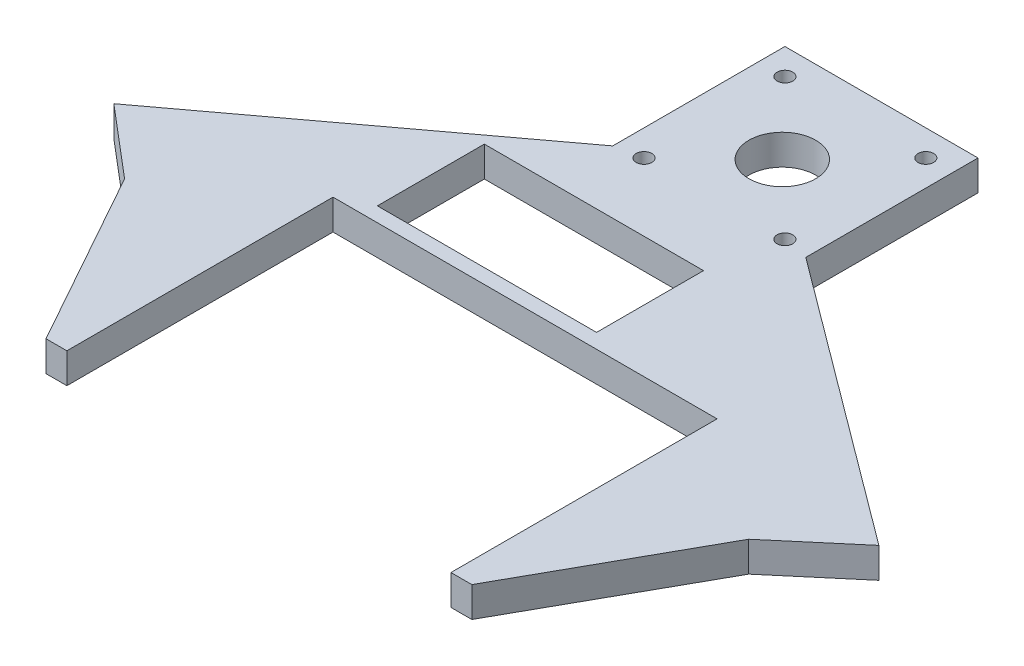
SolidWorks part; units mm, degrees
ref_plane "Plan de face" through (0, 0, 0) normal (0, 0, 1) x (1, 0, 0)
ref_plane "Plan de dessus" through (0, 0, 0) normal (0, 1, 0) x (1, 0, 0)
ref_plane "Plan de droite" through (0, 0, 0) normal (1, 0, 0) x (0, 0, -1)
sketch "Esquisse1" plane through (0, 0, 0) normal (0, 1, 0) x (1, 0, 0)
  line L13 (0, 0) -> (-18.5, 0)
  line L14 (-18.5, 0) -> (-18.5, -33)
  line L15 (-18.5, -33) -> (-73.3, -73.794)
  line L23 (-59.8, -85.2412) -> (-40.8, -119.3)
  line L25 (-36.8, -68.3) -> (0, -68.3)
  line L26 (0, -68.3) -> (0, 0)
  line L27 (-40.8, -119.3) -> (-36.8, -119.3)
  line L28 (-36.8, -119.3) -> (-36.8, -68.3)
  line L30 (-73.3, -73.794) -> (-59.8, -85.2412)
  dimension "D1" = 18.5
  dimension "D2" = 73.3
  dimension "D3" = 68.3
  dimension "D4" = 36.8
  dimension "D5" = 4
  dimension "D6" = 39
  dimension "D7" = 23
  dimension "D8" = 17.7
  dimension "D9" = 51
  dimension "D10" = 33
extrude "Boss.-Extru.1" add sketch "Esquisse1" along normal blind 5.8
sketch "Esquisse2" plane through (0, 5.8, 0) normal (0, 1, 0) x (1, 0, 0)
  line L1 (0, 0) -> (-18.5, 0) construction
  line L3 (-18.5, 0) -> (-18.5, -33) construction
  line L4 (0, -68.3) -> (0, 0) construction
  circle A0 centre (-13.5, -5) radius 1.5
  circle A1 centre (0, -19) radius 6.4
  circle A2 centre (-13.5, -32) radius 1.5
  dimension "D2" = 3
  dimension "D3" = 12.8
  dimension "D6" = 3
  dimension "D1" = 13.5
  dimension "D4" = 19
  dimension "D5" = 5
  dimension "D7" = 27
  dimension "D8" = 5
extrude "Enlèv. mat.-Extru.1" cut sketch "Esquisse2" against normal up to surface (5.8 mm away) up to face at (-31.6111, 0, 63.0261)
mirror "Symétrie2" about plane through (0, 5.8, 68.3) normal (-1, 0, 0) of "Enlèv. mat.-Extru.1", "Boss.-Extru.1"
sketch "Esquisse3" plane through (0, 5.8, 0) normal (0, 1, 0) x (1, 0, 0)
  line L0 (18.5, 0) -> (-18.5, 0) construction
  line L1 (-31.1, -45) -> (10.9, -45)
  line L2 (-31.1, -45) -> (-31.1, -65.5)
  line L3 (-31.1, -65.5) -> (10.9, -65.5)
  line L4 (10.9, -45) -> (10.9, -65.5)
  line L6 (-36.8, -119.3) -> (-36.8, -68.3) construction
  dimension "D1" = 45
  dimension "D2" = 20.5
  dimension "D3" = 42
  dimension "D4" = 5.7
extrude "Enlèv. mat.-Extru.2" cut sketch "Esquisse3" against normal up to surface (5.8 mm away) up to face at (13.5, 0, 6.5)
